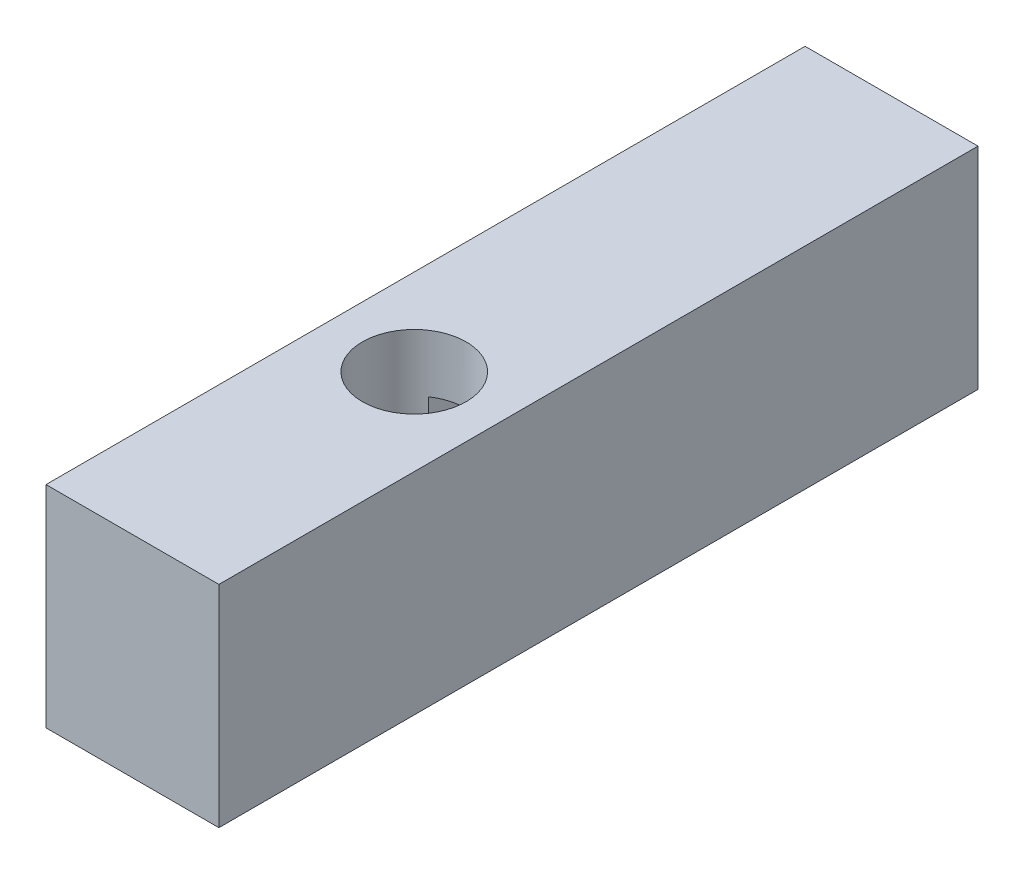
SolidWorks part; units mm, degrees
ref_plane "Front Plane" through (0, 0, 0) normal (0, 0, 1) x (1, 0, 0)
ref_plane "Top Plane" through (0, 0, 0) normal (0, 1, 0) x (1, 0, 0)
ref_plane "Right Plane" through (0, 0, 0) normal (1, 0, 0) x (0, 0, -1)
sketch "Sketch1" plane through (0, 0, 0) normal (1, 0, 0) x (0, 0, -1)
  line L1 (-48.895, 25.4386) -> (82.8131, 25.4386)
  line L2 (-48.895, 25.4386) -> (-48.895, -11.1225)
  line L3 (-48.895, -11.1225) -> (82.8131, -11.1225)
  line L4 (82.8131, 25.4386) -> (82.8131, -11.1225)
extrude "Boss-Extrude1" add sketch "Sketch1" along normal blind 30
shell "Shell1" thickness 10
sketch "Sketch2" plane through (0, 25.4386, 0) normal (0, 1, 0) x (1, 0, 0)
  line L0 (30, 82.8131) -> (0, 82.8131) construction
  line L1 (15, 0) -> (15, 82.8131) construction
  circle A0 centre (15, 0) radius 9
  point P2 (0, 0)
  dimension "D1" = 18
extrude "Cut-Extrude1" cut sketch "Sketch2" against normal through all
